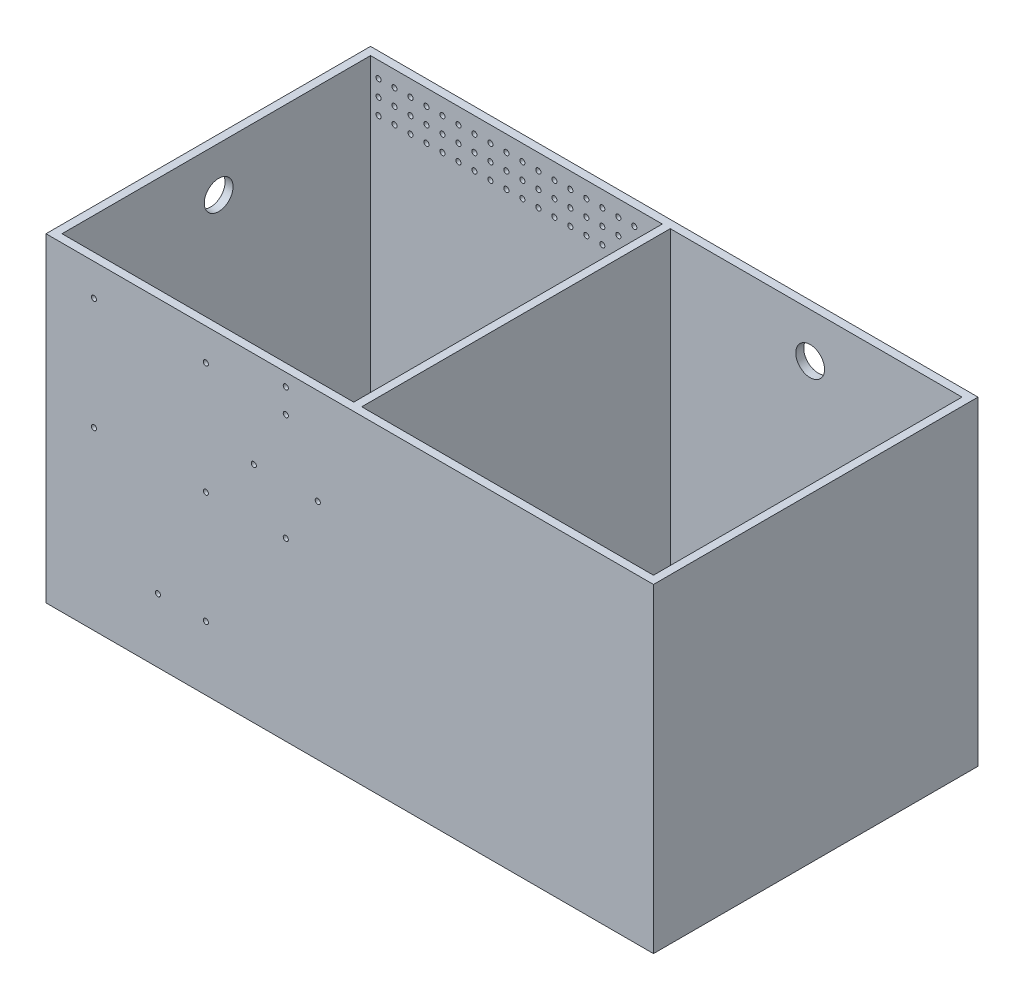
SolidWorks part; units mm, degrees
ref_plane "前视基准面" through (0, 0, 0) normal (0, 0, 1) x (1, 0, 0)
ref_plane "上视基准面" through (0, 0, 0) normal (0, 1, 0) x (1, 0, 0)
ref_plane "右视基准面" through (0, 0, 0) normal (1, 0, 0) x (0, 0, -1)
other "Configuration Table"
sketch "草图1" plane through (0, 0, 0) normal (0, 1, 0) x (1, 0, 0)
  line L0 (-190, 78.5) -> (-190, 101.5)
  line L1 (-167, 101.5) -> (167, 101.5)
  line L2 (-190, 78.5) -> (-190, -78.5)
  line L3 (-167, -101.5) -> (167, -101.5)
  line L4 (190, 78.5) -> (190, -78.5)
  line L5 (-190, 101.5) -> (190, -101.5) construction
  line L6 (-190, -101.5) -> (190, 101.5) construction
  line L7 (-190, 101.5) -> (-167, 101.5)
  line L8 (167, 101.5) -> (190, 101.5)
  line L9 (190, 101.5) -> (190, 78.5)
  line L10 (-190, -78.5) -> (-190, -101.5)
  line L11 (-190, -101.5) -> (-167, -101.5)
  line L12 (190, -78.5) -> (190, -101.5)
  line L13 (190, -101.5) -> (167, -101.5)
  point P0 (0, 0)
  dimension "D1" = 380
  dimension "D2" = 203
extrude "凸台-拉伸1" add sketch "草图1" along normal blind 200
sketch "草图3" plane through (0, 200, 0) normal (0, 1, 0) x (1, 0, 0)
  line L6 (-167, 96.5) -> (167, 96.5)
  line L8 (-185, 78.5) -> (-185, -78.5)
  line L9 (-167, -96.5) -> (167, -96.5)
  line L10 (185, 78.5) -> (185, -78.5)
  line L11 (-185, 96.5) -> (185, -96.5) construction
  line L12 (-185, -96.5) -> (185, 96.5) construction
  line L21 (-190, -101.5) -> (190, -101.5) construction
  line L22 (-190, 101.5) -> (-190, -101.5) construction
  line L23 (-185, 78.5) -> (-185, 96.5)
  line L24 (-185, 96.5) -> (-167, 96.5)
  line L25 (167, 96.5) -> (185, 96.5)
  line L26 (185, 96.5) -> (185, 78.5)
  line L27 (185, -78.5) -> (185, -96.5)
  line L28 (185, -96.5) -> (167, -96.5)
  line L29 (-185, -78.5) -> (-185, -96.5)
  line L30 (-185, -96.5) -> (-167, -96.5)
  point P0 (0, 0)
  point P1 (0, 0)
  dimension "D1" = 370
  dimension "D2" = 193
  dimension "D3" = 5
  dimension "D4" = 5
extrude "切除-拉伸1" cut sketch "草图3" against normal blind 195
sketch "草图9" plane through (190, 0, 0) normal (1, 0, 0) x (0, 0, -1)
sketch "草图11" plane through (0, 0, 101.5) normal (0, 0, 1) x (1, 0, 0)
  line L0 (-190, 200) -> (-190, 0) construction
  line L2 (-160, 180) -> (-90, 180) construction
  line L3 (-160, 180) -> (-160, 110) construction
  line L4 (-160, 110) -> (-90, 110) construction
  line L5 (-90, 180) -> (-90, 110) construction
  line L6 (-190, 200) -> (190, 200) construction
  circle A4 centre (-160, 180) radius 1.6
  circle A5 centre (-90, 180) radius 1.6
  circle A6 centre (-160, 110) radius 1.6
  circle A7 centre (-90, 110) radius 1.6
  dimension "D2" = 70
  dimension "D3" = 70
  dimension "D4" = 20
  dimension "D10" = 30
extrude "切除-拉伸5" cut sketch "草图11" against normal up to next
sketch "草图14" plane through (0, 5, 0) normal (0, 1, 0) x (1, 0, 0)
  line L0 (-185, -96.5) -> (185, -96.5) construction
  line L3 (-2.5, 96.5) -> (2.5, 96.5)
  line L4 (-2.5, 96.5) -> (-2.5, -96.5)
  line L5 (-2.5, -96.5) -> (2.5, -96.5)
  line L6 (2.5, 96.5) -> (2.5, -96.5)
  line L7 (-2.5, 96.5) -> (2.5, -96.5) construction
  line L8 (-2.5, -96.5) -> (2.5, 96.5) construction
  point P0 (0, 0)
  dimension "D1" = 5
extrude "凸台-拉伸2" add sketch "草图14" along normal up to surface (195 mm away) up to face at (0, 200, 0)
sketch "草图15" plane through (0, 0, -101.5) normal (0, 0, -1) x (-1, 0, 0)
  line L0 (-190, 200) -> (190, 200) construction
  line L1 (-190, 0) -> (190, 0) construction
  line L2 (0, 0) -> (0, 200) construction
  line L4 (190, 200) -> (190, 0) construction
  line L6 (23.5, 75) -> (100, 75) construction
  line L7 (23.5, 75) -> (23.5, 20) construction
  line L8 (23.5, 20) -> (100, 20) construction
  line L9 (100, 75) -> (100, 20) construction
  circle A5 centre (23.5, 75) radius 2
  circle A6 centre (100, 75) radius 2
  circle A7 centre (23.5, 20) radius 2
  circle A8 centre (100, 20) radius 2
  dimension "D1" = 76.5
  dimension "D2" = 55
  dimension "D3" = 20
  dimension "D4" = 90
  dimension "D5" = 76.5
  dimension "D9" = 55
extrude "切除-拉伸8" cut sketch "草图15" against normal up to next
sketch "草图17" plane through (-190, 0, 0) normal (-1, 0, 0) x (0, 0, 1)
  line L0 (31.5, 130) -> (31.5, 78) construction
  line L2 (-101.5, 200) -> (101.5, 200) construction
  line L3 (101.5, 200) -> (101.5, 0) construction
  circle A0 centre (31.5, 130) radius 2.5
  circle A2 centre (31.5, 78) radius 2.5
  dimension "D1" = 5
  dimension "D3" = 5
  dimension "D2" = 52
  dimension "D4" = 70
  dimension "D5" = 70
extrude "切除-拉伸10" cut sketch "草图17" against normal up to next
sketch "草图19" plane through (0, 0, -101.5) normal (0, 0, -1) x (-1, 0, 0)
  line L0 (-190, 200) -> (190, 200) construction
  line L4 (-190, 200) -> (-190, 0) construction
  line L6 (91.75, 125.5) -> (91.75, 118.5) construction
  line L7 (91.75, 122) -> (190, 122) construction
  line L8 (190, 200) -> (190, 0) construction
  circle A0 centre (-90, 172) radius 9
  dimension "D3" = 18
  dimension "D1" = 28
  dimension "D2" = 100
  dimension "D4" = 98.25
extrude "切除-拉伸11" cut sketch "草图19" against normal up to next
sketch "草图20" plane through (-190, 0, 0) normal (-1, 0, 0) x (0, 0, 1)
  line L0 (-101.5, 200) -> (-101.5, 0) construction
  line L2 (-101.5, 200) -> (101.5, 200) construction
  circle A0 centre (-1.5, 172) radius 9
  dimension "D3" = 18
  dimension "D1" = 100
  dimension "D2" = 28
extrude "切除-拉伸12" cut sketch "草图20" against normal up to next
sketch "草图21" plane through (0, 0, 101.5) normal (0, 0, 1) x (1, 0, 0)
  line L0 (0, 200) -> (0, 0) construction
  line L1 (-190, 200) -> (190, 200) construction
  line L2 (-40, 110) -> (-40, 200) construction
  line L3 (-60, 140) -> (-20, 140) construction
  circle A0 centre (-40, 110) radius 1.6
  circle A1 centre (-20, 140) radius 1.6
  circle A2 centre (-60, 140) radius 1.6
  dimension "D1" = 40
  dimension "D2" = 3.2
  dimension "D5" = 3.2
  dimension "D6" = 3.2
  dimension "D3" = 90
  dimension "D4" = 20
  dimension "D7" = 40
  dimension "D8" = 30
extrude "切除-拉伸13" cut sketch "草图21" against normal up to next
sketch "草图22" plane through (0, 0, 101.5) normal (0, 0, 1) x (1, 0, 0)
  line L0 (0, 0) -> (0, 200) construction
  line L1 (-190, 200) -> (190, 200) construction
  line L4 (-40, 192) -> (-40, 177) construction
  circle A0 centre (-40, 192) radius 1.6
  circle A1 centre (-40, 177) radius 1.6
  circle A2 centre (-40, 110) radius 1.6 construction
  dimension "D1" = 3.2
  dimension "D3" = 3.2
  dimension "D2" = 8
  dimension "D4" = 15
  dimension "D5" = 40
  dimension "D6" = 67
extrude "切除-拉伸14" cut sketch "草图22" against normal up to next
sketch "草图24" plane through (0, 0, 101.5) normal (0, 0, 1) x (1, 0, 0)
  line L0 (-190, 200) -> (-190, 0) construction
  line L1 (-120, 40) -> (-90, 40) construction
  line L2 (-190, 0) -> (190, 0) construction
  circle A0 centre (-120, 40) radius 1.6
  circle A1 centre (-90, 40) radius 1.6
  dimension "D1" = 3.2
  dimension "D2" = 70
  dimension "D3" = 30
  dimension "D4" = 40
extrude "切除-拉伸15" cut sketch "草图24" against normal up to next
sketch "草图25" plane through (0, 0, -101.5) normal (0, 0, -1) x (-1, 0, 0)
  line L0 (0, 0) -> (0, 200) construction
  line L1 (-190, 200) -> (190, 200) construction
  line L2 (190, 200) -> (190, 0) construction
  circle A0 centre (180, 190) radius 1.6
  circle A1 centre (170, 190) radius 1.6
  circle A2 centre (160, 190) radius 1.6
  circle A3 centre (150, 190) radius 1.6
  circle A4 centre (140, 190) radius 1.6
  circle A5 centre (130, 190) radius 1.6
  circle A6 centre (120, 190) radius 1.6
  circle A7 centre (110, 190) radius 1.6
  circle A8 centre (100, 190) radius 1.6
  circle A9 centre (90, 190) radius 1.6
  circle A10 centre (80, 190) radius 1.6
  circle A11 centre (70, 190) radius 1.6
  circle A12 centre (60, 190) radius 1.6
  circle A13 centre (50, 190) radius 1.6
  circle A14 centre (40, 190) radius 1.6
  circle A15 centre (30, 190) radius 1.6
  circle A16 centre (20, 190) radius 1.6
  circle A17 centre (10, 190) radius 1.6
  circle A18 centre (170, 180) radius 1.6
  circle A19 centre (160, 180) radius 1.6
  circle A20 centre (150, 180) radius 1.6
  circle A21 centre (140, 180) radius 1.6
  circle A22 centre (130, 180) radius 1.6
  circle A23 centre (120, 180) radius 1.6
  circle A24 centre (110, 180) radius 1.6
  circle A25 centre (100, 180) radius 1.6
  circle A26 centre (90, 180) radius 1.6
  circle A27 centre (80, 180) radius 1.6
  circle A28 centre (70, 180) radius 1.6
  circle A29 centre (60, 180) radius 1.6
  circle A30 centre (50, 180) radius 1.6
  circle A31 centre (40, 180) radius 1.6
  circle A32 centre (30, 180) radius 1.6
  circle A33 centre (20, 180) radius 1.6
  circle A34 centre (10, 180) radius 1.6
  circle A35 centre (180, 180) radius 1.6
  circle A36 centre (80, 170) radius 1.6
  circle A37 centre (110, 170) radius 1.6
  circle A38 centre (40, 170) radius 1.6
  circle A39 centre (130, 170) radius 1.6
  circle A40 centre (70, 170) radius 1.6
  circle A41 centre (170, 170) radius 1.6
  circle A42 centre (10, 170) radius 1.6
  circle A43 centre (20, 170) radius 1.6
  circle A44 centre (120, 170) radius 1.6
  circle A45 centre (90, 170) radius 1.6
  circle A46 centre (140, 170) radius 1.6
  circle A47 centre (60, 170) radius 1.6
  circle A48 centre (100, 170) radius 1.6
  circle A49 centre (160, 170) radius 1.6
  circle A50 centre (180, 170) radius 1.6
  circle A51 centre (30, 170) radius 1.6
  circle A52 centre (150, 170) radius 1.6
  circle A53 centre (50, 170) radius 1.6
  dimension "D2" = 3.2
  dimension "D1" = 190
  dimension "D3" = 10
  dimension "D4" = 10
  dimension "D5" = 18
  dimension "D6" = 2
extrude "切除-拉伸16" cut sketch "草图25" against normal up to next (5 mm away)
